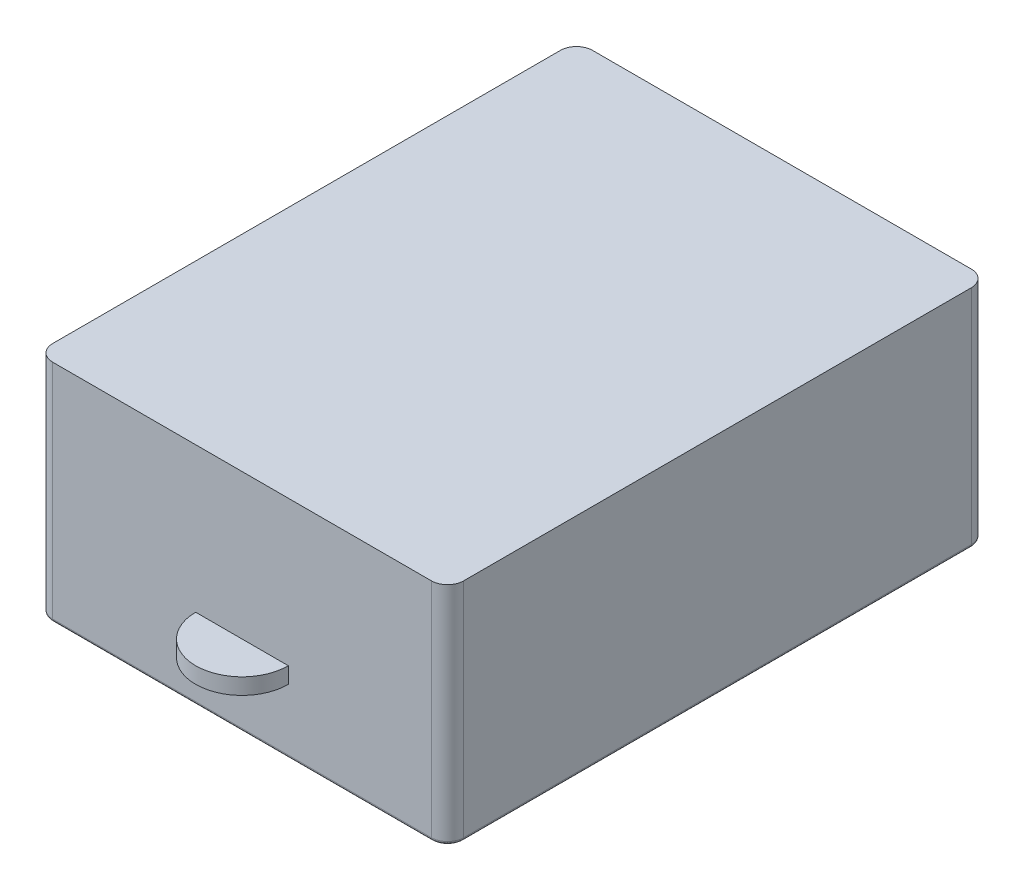
SolidWorks part; units mm, degrees
ref_plane "Front Plane" through (0, 0, 0) normal (0, 0, 1) x (1, 0, 0)
ref_plane "Top Plane" through (0, 0, 0) normal (0, 1, 0) x (1, 0, 0)
ref_plane "Right Plane" through (0, 0, 0) normal (1, 0, 0) x (0, 0, -1)
sketch "lid" plane through (0, 0, 0) normal (0, 1, 0) x (1, 0, 0)
  line L0 (-11, 23.35) -> (-11, -7.65)
  line L1 (13, -7.9) -> (13, 23.35)
  line L3 (-10.5, -8.15) -> (12.567, -8.15)
  line L5 (-10.5, 23.85) -> (12.5, 23.85)
  line L13 (-10.75, 24.6) -> (12.75, 24.6)
  line L14 (-11.75, 23.6) -> (-11.75, -7.9)
  line L15 (-10.75, -8.9) -> (12.75, -8.9)
  line L16 (13.75, 23.6) -> (13.75, -7.9)
  arc A0 (13.75, -7.9) -> (12.75, -8.9) centre (12.75, -7.9) cw
  arc A1 (-11.75, -7.9) -> (-10.75, -8.9) centre (-10.75, -7.9) ccw
  arc A2 (13, 23.35) -> (12.5, 23.85) centre (12.5, 23.35) ccw
  arc A3 (-10.5, 23.85) -> (-11, 23.35) centre (-10.5, 23.35) ccw
  arc A4 (-11.75, 23.6) -> (-10.75, 24.6) centre (-10.75, 23.6) cw
  arc A5 (12.75, 24.6) -> (13.75, 23.6) centre (12.75, 23.6) cw
  arc A6 (-11, -7.65) -> (-10.5, -8.15) centre (-10.5, -7.65) ccw
  arc A7 (12.567, -8.15) -> (13, -7.9) centre (12.567, -7.65) ccw
  point P0 (0, -8.9)
extrude "Boss-Extrude33" add sketch "lid" along normal blind 5 contours A0 A1 | A5 A3 L5 A2 region at (1, 0, -24.179)
extrude "Boss-Extrude34" add sketch "lid<5>" along normal blind 1 from offset 5 contours A2 L5 A3 A0 | A0 A1 | A5 A3 L5 A2 region at (1.0003, 0, -7.8495) region at (1, 0, -24.179)
sketch "lid<5>" plane through (0, 0, 0) normal (0, 1, 0) x (1, 0, 0) same geometry as "lid"
extrude "Boss-Extrude35" add sketch "lid<7>" against normal blind 8
sketch "lid<7>" plane through (0, 0, 0) normal (0, 1, 0) x (1, 0, 0) same geometry as "lid"
sketch "Sketch20" plane through (0, 6, 0) normal (0, 1, 0) x (1, 0, 0)
  line L0 (-6.5, -4.5) -> (8.5, -4.5) construction
  line L1 (-6.5, -3) -> (8.5, -3)
  line L2 (-6.5, -6) -> (8.5, -6)
  arc A0 (-6.5, -3) -> (-6.5, -6) centre (-6.5, -4.5) ccw
  arc A1 (8.5, -6) -> (8.5, -3) centre (8.5, -4.5) ccw
  point P2 (1, -4.5)
ref_plane "Plane1" through (0, -4, 0) normal (0, 1, 0) x (1, 0, 0)
sketch "Sketch27" plane through (0, -4, 0) normal (0, 1, 0) x (1, 0, 0)
  line L0 (-10.75, -8.9) -> (12.75, -8.9) construction
  line L1 (12.75, 24.6) -> (-10.75, 24.6) construction
  line L2 (-1.875, -8.9) -> (3.875, -8.9)
  line L3 (4.125, 24.6) -> (-2.125, 24.6)
  arc A0 (-1.875, -8.9) -> (3.875, -8.9) centre (1, -8.9) ccw
  arc A1 (4.125, 24.6) -> (-2.125, 24.6) centre (1, 24.6) ccw
extrude "Boss-Extrude40" add sketch "Sketch27" along normal blind 1
fillet "Fillet2" radius 0.2 16 edges at (13.75, -8, -7.85) (13.4571, -8, -24.3071) (1, -8, -24.6) (-11.4571, -8, -24.3071) (-11.75, -8, -7.85) (-11.4571, -8, 8.6071) (1, -8, 8.9) (13.4571, -8, 8.6071) (13, -8, -7.725) (12.817, -8, 8.083) (1.0335, -8, 8.15) (-10.8536, -8, 8.0036) (-11, -8, -7.85) (-10.8536, -8, -23.7036) (1, -8, -23.85) (12.8536, -8, -23.7036)
